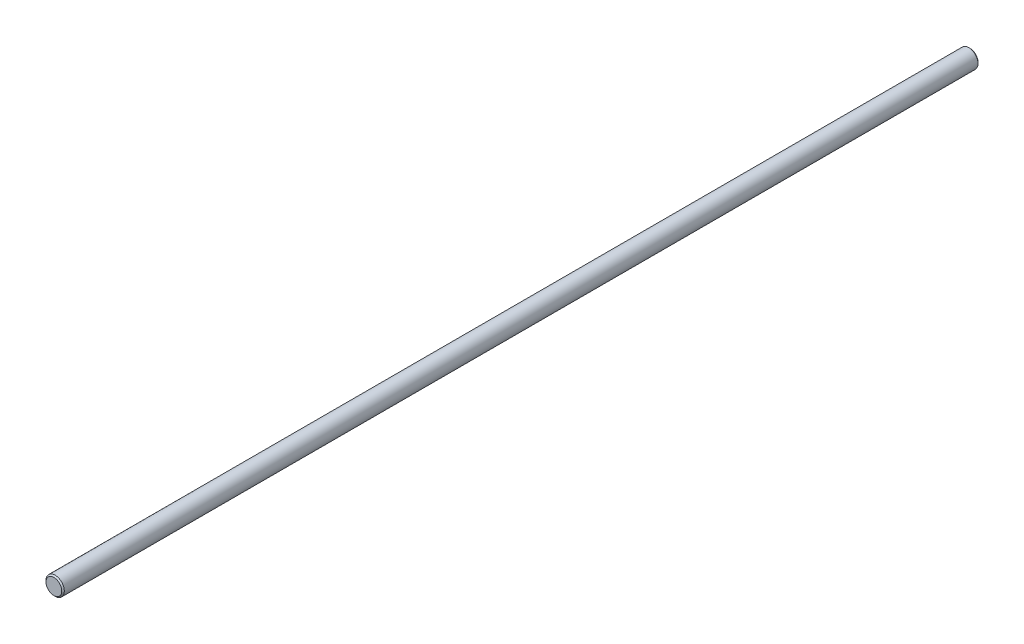
SolidWorks part; units mm, degrees
ref_plane "Front Plane" through (0, 0, 0) normal (0, 0, 1) x (1, 0, 0)
ref_plane "Top Plane" through (0, 0, 0) normal (0, 1, 0) x (1, 0, 0)
ref_plane "Right Plane" through (0, 0, 0) normal (1, 0, 0) x (0, 0, -1)
sketch "Sketch1" plane through (0, 0, 0) normal (0, 0, 1) x (1, 0, 0)
  line L0 (-3, 0) -> (3, 0) construction
  line L5 (0, 3) -> (0, -3) construction
  circle A1 centre (0, 0) radius 3
  point P7 (-3, 0)
  point P8 (3, 0)
  point P12 (0, -3)
  point P13 (0, 3)
  dimension "Diameter" = 6
sketch "Sketch2" plane through (0, 0, 0) normal (1, 0, 0) x (0, 0, -1)
  line L0 (-94, -3) -> (-94, 3) construction
  line L1 (100, -3) -> (-100, -3)
  line L2 (100, -3) -> (100, 3)
  line L3 (100, 3) -> (-100, 3)
  line L4 (-100, -3) -> (-100, 3)
  line L5 (100, -3) -> (-100, 3) construction
  line L6 (100, 3) -> (-100, -3) construction
  line L7 (94, -3) -> (94, 3) construction
  line L8 (-100, 2.58) -> (-99.58, 3) construction
  point P0 (0, 0)
  point P8 (-100, 3)
  point P9 (100, 3)
  point P14 (-94, 3)
  point P15 (-94, -3)
  point P16 (94, 3)
  point P17 (94, -3)
  point P25 (0, -3)
  dimension "Length" = 200
  dimension "D1" = 6
  dimension "D2" = 6
  dimension "Chamfer Typ," = 45
  dimension "D4" = 0.42
sketch "Sketch3" plane through (0, 0, 0) normal (0, 0, 1) x (1, 0, 0)
  circle A0 centre (0, 0) radius 3 construction
  circle A1 centre (0, 0) radius 3
extrude "Boss-Extrude1" add sketch "Sketch3" along normal blind 150 and the other way blind 150
chamfer "Chamfer1" distance 0.42 angle 45 2 edges at (3, 0, -150) (3, 0, 150)
equation "\"D1@Sketch2\"=\"Diameter@Sketch1\""
equation "\"D2@Sketch2\"=\"Diameter@Sketch1\""
equation "\"D1@Chamfer1\"=\"Diameter@Sketch1\"*.07"
equation "\"D4@Sketch2\"=\"Diameter@Sketch1\"*.07"
equation "\"D2@Chamfer1\"=\"Chamfer Typ,@Sketch2\""
